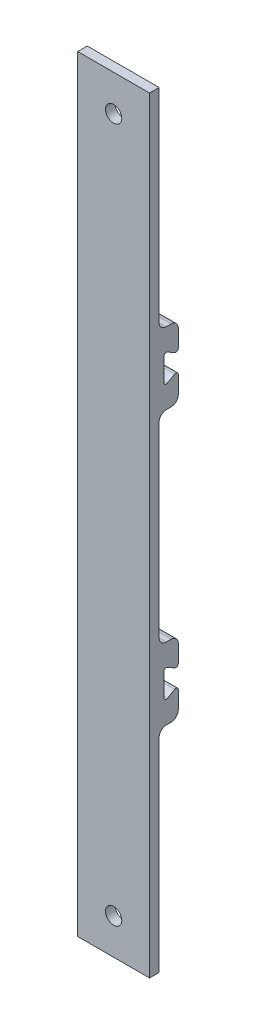
SolidWorks part; units mm, degrees
material "ABS"
ref_plane "Спереди" through (0, 0, 0) normal (0, 0, 1) x (1, 0, 0)
ref_plane "Сверху" through (0, 0, 0) normal (0, 1, 0) x (1, 0, 0)
ref_plane "Справа" through (0, 0, 0) normal (1, 0, 0) x (0, 0, -1)
sketch "Эскиз1" plane through (0, 0, 0) normal (0, 0, 1) x (1, 0, 0)
  line L1 (0, 160) -> (15, 160)
  line L2 (0, 160) -> (0, 0)
  line L3 (0, 0) -> (15, 0)
  line L4 (15, 160) -> (15, 0)
  dimension "D1" = 160
  dimension "D2" = 15
extrude "Бобышка-Вытянуть1" add sketch "Эскиз1" against normal blind 2
fillet "Скругление1" [suppressed] radius 6
sketch "Эскиз4" plane through (15, 0, 0) normal (1, 0, 0) x (0, 0, -1)
  line L0 (0, 160) -> (0, 0) construction
  line L1 (0, 116) -> (6, 116)
  line L2 (0, 116) -> (0, 101)
  line L3 (0, 101) -> (6, 101)
  line L4 (6, 116) -> (6, 101)
  line L6 (0, 59) -> (6, 59)
  line L7 (0, 59) -> (0, 44)
  line L8 (0, 44) -> (6, 44)
  line L9 (6, 59) -> (6, 44)
  point P10 (8.18, 124.29)
  point P14 (6.944, 126)
  dimension "D1" = 15
  dimension "D2" = 44
  dimension "D3" = 44
  dimension "D4" = 6
extrude "Бобышка-Вытянуть2" add sketch "Эскиз4" along direction (-1, 0, 0) on the side against the normal up to surface (15 mm away) up to face at (0, 80, -1)
sketch "Эскиз3" plane through (15, 0, 0) normal (1, 0, 0) x (0, 0, -1)
  line L1 (2, 44) -> (6, 44) construction
  line L10 (6, 110) -> (3, 111.7321)
  line L11 (6, 101) -> (6, 116) construction
  line L12 (3, 111.7321) -> (3, 105.2679)
  line L13 (3, 105.2679) -> (6, 107)
  line L14 (6, 107) -> (6, 110)
  line L15 (6, 53) -> (3, 54.7321)
  line L16 (6, 44) -> (6, 59) construction
  line L17 (3, 54.7321) -> (3, 48.2679)
  line L18 (3, 48.2679) -> (6, 50)
  line L19 (6, 50) -> (6, 53)
  point P13 (6, 64.5623)
  dimension "D1" = 3
  dimension "D2" = 60
  dimension "D3" = 3
  dimension "D4" = 6
  dimension "D5" = 6
fillet "Скругление3" radius 1.5 8 edges at (7.5, 59, -2) (7.5, 44, -2) (7.5, 44, -6) (7.5, 59, -6) (7.5, 101, -2) (7.5, 101, -6) (7.5, 116, -6) (7.5, 116, -2)
sketch "Эскиз5" plane through (0, 0, -2) normal (0, 0, -1) x (-1, 0, 0)
  line L0 (-15, 160) -> (0, 160) construction
  line L2 (0, 0) -> (-15, 0) construction
  line L3 (0, 160) -> (0, 117.5) construction
  point P0 (-7.5, 152.5)
  point P1 (-7.5, 7.5)
  point P2 (0, 0)
  point P7 (8.9865, 158.6006)
  dimension "D1" = 7.5
  dimension "D2" = 7.5
  dimension "D3" = 7.5
hole_wizard "Отверстие с зазором M31" positions "Эскиз6" profile "Эскиз7" hole size "M3" standard "DIN" end condition through all
sketch "Эскиз6" plane through (0, 0, -2) normal (0, 0, -1) x (-1, 0, 0)
  point P0 (-7.5, 152.5)
  point P3 (-7.5, 7.5)
sketch "Эскиз7" plane through (7.5, 152.5, -2) normal (1, 0, 0) x (0, 1, 0)
  line L0 (0, 0) -> (0, 2)
  line L1 (0, 2) -> (1.7, 2)
  line L2 (1.7, 2) -> (1.7, 0)
  line L5 (1.7, 0) -> (0, 0)
  line L11 (0, -6.35) -> (0, 107.95) construction
  dimension "Диаметр сквозного отверстия" = 3.4
  dimension "Глубина сквозного отверстия" = 2
extrude "Вырез-Вытянуть2" cut sketch "Эскиз3" against normal blind 13.5
fillet "Скругление4" radius 0.5 8 edges at (8.25, 107, -6) (8.25, 105.2679, -3) (8.25, 111.7321, -3) (8.25, 110, -6) (8.25, 48.2679, -3) (8.25, 54.7321, -3) (8.25, 50, -6) (8.25, 53, -6)
